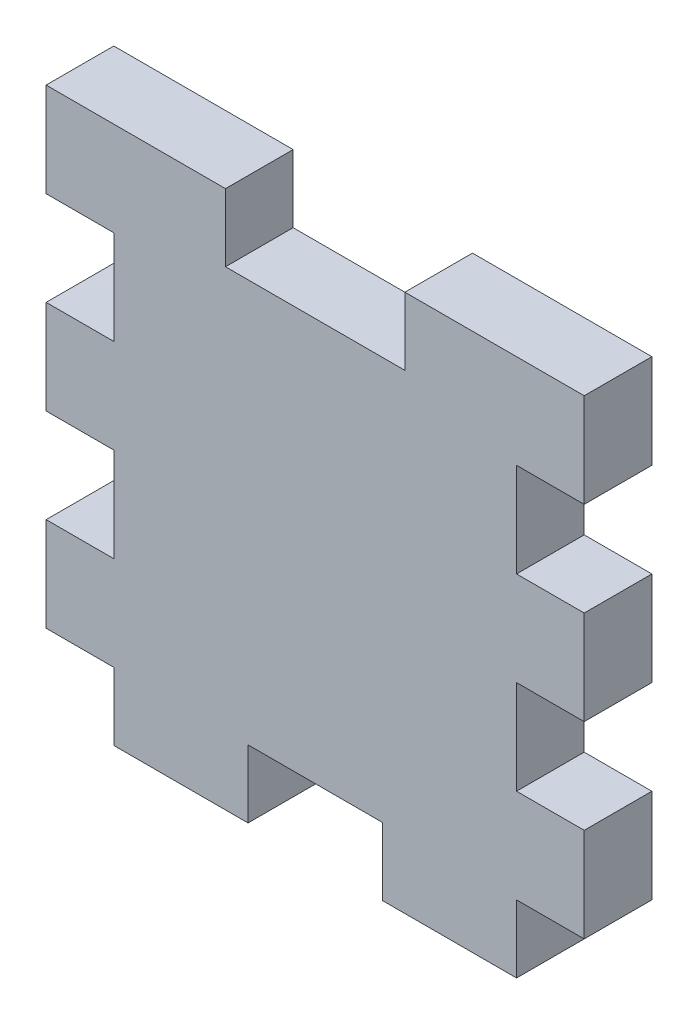
SolidWorks part; units mm, degrees
ref_plane "Front Plane" through (0, 0, 0) normal (0, 0, 1) x (1, 0, 0)
ref_plane "Top Plane" through (0, 0, 0) normal (0, 1, 0) x (1, 0, 0)
ref_plane "Right Plane" through (0, 0, 0) normal (1, 0, 0) x (0, 0, -1)
sketch "Sketch1" plane through (0, 0, 0) normal (0, 0, 1) x (1, 0, 0)
  line L0 (15.875, 15.875) -> (-15.875, 15.875)
  line L1 (-15.875, -15.875) -> (15.875, -15.875)
  line L2 (-15.875, -15.875) -> (-15.875, 15.875)
  line L4 (15.875, -15.875) -> (15.875, 15.875)
  line L5 (-15.875, -15.875) -> (15.875, 15.875) construction
  line L6 (-15.875, 15.875) -> (15.875, -15.875) construction
  point P0 (0, 0)
  dimension "D1" = 31.75
  dimension "D2" = 31.75
extrude "Boss-Extrude1" add sketch "Sketch1" along normal blind 5.334
sketch "Sketch4" plane through (0, 0, 5.334) normal (0, 0, 1) x (1, 0, 0)
  line L1 (-15.875, -15.875) -> (-15.875, 15.875)
  line L2 (-15.875, 15.875) -> (15.875, 15.875)
  line L3 (15.875, 15.875) -> (-15.875, 15.875) construction
  line L4 (-15.875, 21.209) -> (15.875, 21.209)
  line L5 (15.875, 15.875) -> (15.875, -15.875)
  line L6 (-15.875, -15.875) -> (-21.209, -15.875)
  line L8 (15.875, -15.875) -> (-15.875, -15.875)
  line L9 (-15.875, 21.209) -> (-21.209, 21.209)
  line L10 (-21.209, -15.875) -> (-21.209, 21.209)
  line L11 (15.875, 21.209) -> (21.209, 21.209)
  line L12 (-15.875, 15.875) -> (-15.875, 21.209) construction
  line L13 (15.875, -15.875) -> (21.209, -15.875)
  line L14 (21.209, 21.209) -> (21.209, -15.875)
  line L16 (15.875, -15.875) -> (15.875, -21.209)
  line L17 (15.875, -21.209) -> (-15.875, -21.209)
  line L18 (-15.875, -15.875) -> (-15.875, -21.209)
  line M1 (15.875, -15.875) -> (15.875, 15.875)
  line M2 (15.875, 15.875) -> (-15.875, 15.875)
  line M3 (-15.875, 15.875) -> (-15.875, -15.875)
  line M4 (-15.875, -15.875) -> (15.875, -15.875)
  dimension "D1" = 5.334
  dimension "D2" = 5.334
  dimension "D3" = 5.334
  dimension "D4" = 5.334
  dimension "D5" = 5.334
extrude "Boss-Extrude6" add sketch "Sketch4" against normal through all contours L12 L9 L10 L6 M3 | L12 L13 L14 L11 L4 M2 M1 | L18 L17 L16 M4 region at (-18.542, 2.667, 5.334) region at (0, -18.542, 5.334) region at (-15.3506, 18.542, 5.334)
sketch "Sketch7" plane through (0, 0, 5.334) normal (0, 0, 1) x (1, 0, 0)
  line L0 (-21.209, -15.875) -> (-21.209, 21.209) construction
  line L1 (-21.209, -8.4582) -> (-15.875, -8.4582)
  line L2 (-21.209, -8.4582) -> (-21.209, -1.0414)
  line L3 (-21.209, -1.0414) -> (-15.875, -1.0414)
  line L4 (-15.875, -8.4582) -> (-15.875, -1.0414)
  line L5 (-15.875, -15.875) -> (-15.875, -8.4582) construction
  line L6 (-21.209, 6.3754) -> (-15.875, 6.3754)
  line L7 (-21.209, 6.3754) -> (-21.209, 13.7922)
  line L8 (-21.209, 13.7922) -> (-15.875, 13.7922)
  line L9 (-15.875, 6.3754) -> (-15.875, 13.7922)
  line L10 (-15.875, -1.0414) -> (-15.875, 6.3754) construction
  line L11 (21.209, 21.209) -> (-21.209, 21.209) construction
  line L12 (-15.875, 13.7922) -> (-15.875, 21.209) construction
  line L13 (0, 0) -> (0, 21.209) construction
  line L14 (15.875, 13.7922) -> (15.875, 21.209) construction
  line L15 (15.875, -1.0414) -> (15.875, 6.3754) construction
  line L16 (15.875, -15.875) -> (15.875, -8.4582) construction
  line L17 (15.875, 6.3754) -> (15.875, 13.7922)
  line L18 (21.209, 13.7922) -> (15.875, 13.7922)
  line L19 (21.209, 6.3754) -> (21.209, 13.7922)
  line L20 (21.209, 6.3754) -> (15.875, 6.3754)
  line L21 (15.875, -8.4582) -> (15.875, -1.0414)
  line L22 (21.209, -1.0414) -> (15.875, -1.0414)
  line L23 (21.209, -8.4582) -> (21.209, -1.0414)
  line L24 (21.209, -8.4582) -> (15.875, -8.4582)
extrude "Cut-Extrude2" cut sketch "Sketch7" against normal through all
sketch "Sketch8" plane through (0, 0, 5.334) normal (0, 0, 1) x (1, 0, 0)
  line L1 (21.209, 21.209) -> (-21.209, 21.209) construction
  line L2 (-7.0697, 21.209) -> (7.0697, 21.209)
  line L3 (-7.0697, 21.209) -> (-7.0697, 15.875)
  line L4 (-7.0697, 15.875) -> (7.0697, 15.875)
  line L5 (7.0697, 21.209) -> (7.0697, 15.875)
  line L11 (-7.0697, 15.875) -> (-21.209, 15.875) construction
  line L16 (-21.209, 13.7922) -> (-21.209, 21.209) construction
  line L17 (7.0697, 15.875) -> (21.209, 15.875) construction
  line L18 (21.209, 21.209) -> (21.209, 13.7922) construction
  dimension "D1" = 5.334
extrude "Cut-Extrude3" cut sketch "Sketch8" against normal through all
sketch "Sketch9" plane through (0, 0, 5.334) normal (0, 0, 1) x (1, 0, 0)
  line L2 (15.875, -21.209) -> (-15.875, -21.209) construction
  line L3 (-5.2917, -15.875) -> (5.2917, -15.875)
  line L4 (-5.2917, -15.875) -> (-5.2917, -21.209)
  line L5 (-5.2917, -21.209) -> (5.2917, -21.209)
  line L6 (5.2917, -15.875) -> (5.2917, -21.209)
  line L7 (-5.2917, -15.875) -> (-15.875, -15.875) construction
  line L8 (5.2917, -15.875) -> (15.875, -15.875) construction
extrude "Cut-Extrude5" cut sketch "Sketch9" against normal through all
equation "\"D1@Boss-Extrude1\"=\"material\""
equation "\"material\"=\"MDF@Platform.assembly\""
